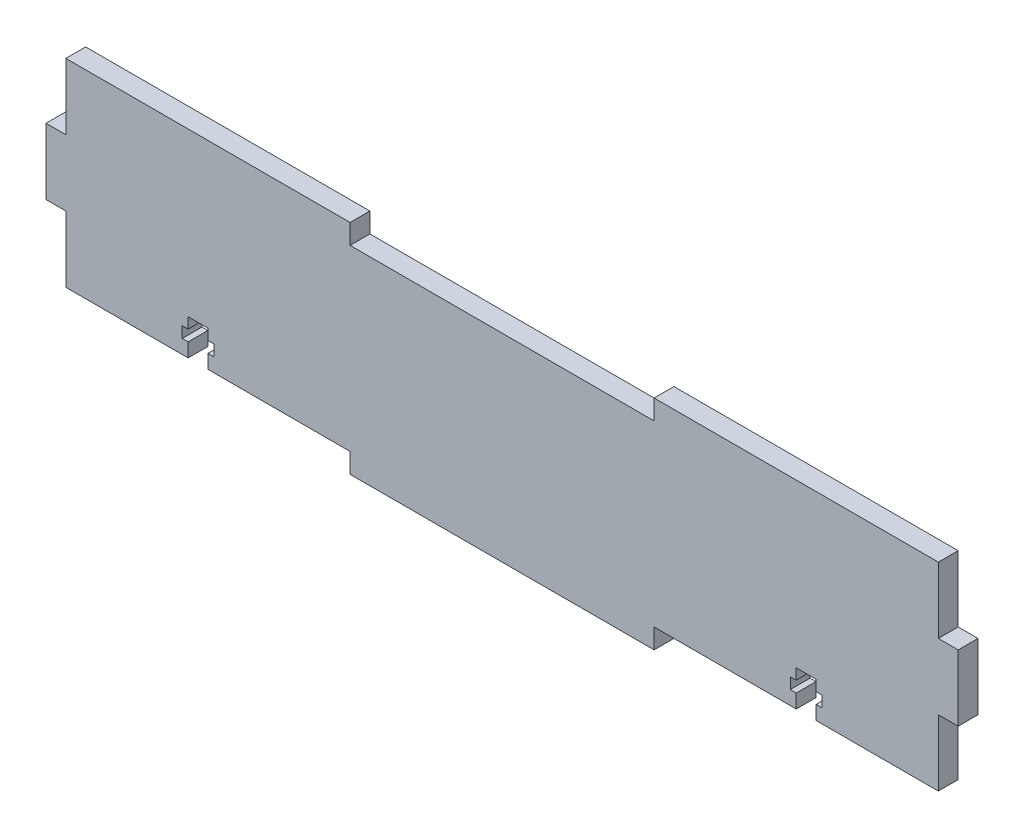
SolidWorks part; units mm, degrees
ref_plane "Alzado" through (0, 0, 0) normal (0, 0, 1) x (1, 0, 0)
ref_plane "Planta" through (0, 0, 0) normal (0, 1, 0) x (1, 0, 0)
ref_plane "Vista lateral" through (0, 0, 0) normal (1, 0, 0) x (0, 0, -1)
sketch "Croquis1" plane through (0, 0, 0) normal (0, 0, 1) x (1, 0, 0)
  line L0 (115, 0) -> (115, 23.3303) construction
  line L1 (0, 0) -> (230, 0)
  line L2 (0, 0) -> (0, 55)
  line L3 (0, 55) -> (230, 55)
  line L4 (230, 0) -> (230, 55)
  line L5 (0, 55) -> (5, 55)
  line L6 (0, 55) -> (0, 0)
  line L7 (0, 0) -> (5, 0)
  line L8 (5, 55) -> (5, 0)
  line L9 (225, 55) -> (225, 0)
  line L10 (76.6667, 5) -> (76.6667, 0)
  line L11 (0, 0) -> (230, 0)
  line L12 (0, 0) -> (0, 5)
  line L13 (0, 5) -> (230, 5)
  line L14 (230, 0) -> (230, 5)
  line L15 (153.3333, 0) -> (153.3333, 5)
  line L16 (0, 38.3333) -> (5, 38.3333)
  line L17 (5, 21.6667) -> (0, 21.6667)
  line L18 (225, 21.6667) -> (230, 21.6667)
  line L19 (230, 38.3333) -> (225, 38.3333)
  point P21 (2.5, 38.3333)
  dimension "D1" = 230
  dimension "D2" = 55
  dimension "D3" = 5
  dimension "D4" = 5
  dimension "D5" = 76.6667
  dimension "D6" = 76.6667
  dimension "D7" = 16.6667
  dimension "D8" = 16.6667
extrude "Saliente-Extruir1" add sketch "Croquis1" along normal blind 5 contours L17 L8 L16 L2 | L4 L19 L9 L18 | L0 L11 L15 L13 | L1 L0 L13 L10 | L8 L13 L9 L3 region at (95.8333, 2.5, 0) region at (134.1667, 2.5, 0) region at (115, 30, 0) region at (2.5, 30, 0) region at (227.5, 30, 0)
sketch "Croquis2" plane through (0, 0, 5) normal (0, 0, 1) x (1, 0, 0)
  line L0 (38.3333, 5) -> (38.3333, 14) construction
  line L1 (5, 5) -> (76.6667, 5) construction
  line L2 (115, 0) -> (115, 11.3726) construction
  line L3 (76.6667, 0) -> (153.3333, 0) construction
  line L4 (35.8333, 5) -> (35.8333, 8.5)
  line L5 (35.8333, 8.5) -> (34.3333, 8.5)
  line L6 (34.3333, 8.5) -> (34.3333, 11.3)
  line L7 (34.3333, 11.3) -> (35.8333, 11.3)
  line L8 (35.8333, 11.3) -> (35.8333, 14)
  line L9 (35.8333, 14) -> (40.8333, 14)
  line L10 (40.8333, 11.3) -> (40.8333, 14)
  line L11 (42.3333, 11.3) -> (40.8333, 11.3)
  line L12 (42.3333, 8.5) -> (42.3333, 11.3)
  line L13 (40.8333, 8.5) -> (42.3333, 8.5)
  line L14 (40.8333, 5) -> (40.8333, 8.5)
  line L15 (191.6667, 5) -> (191.6667, 14) construction
  line L16 (189.1667, 5) -> (189.1667, 8.5)
  line L17 (189.1667, 8.5) -> (187.6667, 8.5)
  line L18 (187.6667, 8.5) -> (187.6667, 11.3)
  line L19 (187.6667, 11.3) -> (189.1667, 11.3)
  line L20 (189.1667, 11.3) -> (189.1667, 14)
  line L21 (194.1667, 14) -> (189.1667, 14)
  line L22 (194.1667, 11.3) -> (194.1667, 14)
  line L23 (195.6667, 11.3) -> (194.1667, 11.3)
  line L24 (195.6667, 8.5) -> (195.6667, 11.3)
  line L25 (194.1667, 8.5) -> (195.6667, 8.5)
  line L26 (194.1667, 5) -> (194.1667, 8.5)
  line L27 (40.8333, 5) -> (35.8333, 5)
  line L28 (194.1667, 5) -> (189.1667, 5)
  line L29 (0, 21.6667) -> (0, 38.3333) construction
  point P10 (35.0833, 11.3)
  point P16 (0, 0)
  point P38 (38.3333, 9.5)
  dimension "D1" = 2.8
  dimension "D2" = 4
  dimension "D3" = 9
  dimension "D4" = 3.5
  dimension "D5" = 2.5
  dimension "D6" = 38.3333
extrude "Cortar-Extruir1" cut sketch "Croquis2" against normal blind 5
sketch "Croquis3" plane through (0, 0, 5) normal (0, 0, 1) x (1, 0, 0)
  line L0 (5, 55) -> (225, 55) construction
  line L1 (76.6667, 55) -> (153.3333, 55)
  line L2 (76.6667, 55) -> (76.6667, 50)
  line L3 (76.6667, 50) -> (153.3333, 50)
  line L4 (153.3333, 55) -> (153.3333, 50)
  line L5 (0, 21.6667) -> (0, 38.3333) construction
  line L6 (230, 21.6667) -> (230, 38.3333) construction
  dimension "D1" = 5
  dimension "D2" = 76.6667
  dimension "D3" = 76.6667
extrude "Cortar-Extruir2" cut sketch "Croquis3" against normal blind 10
